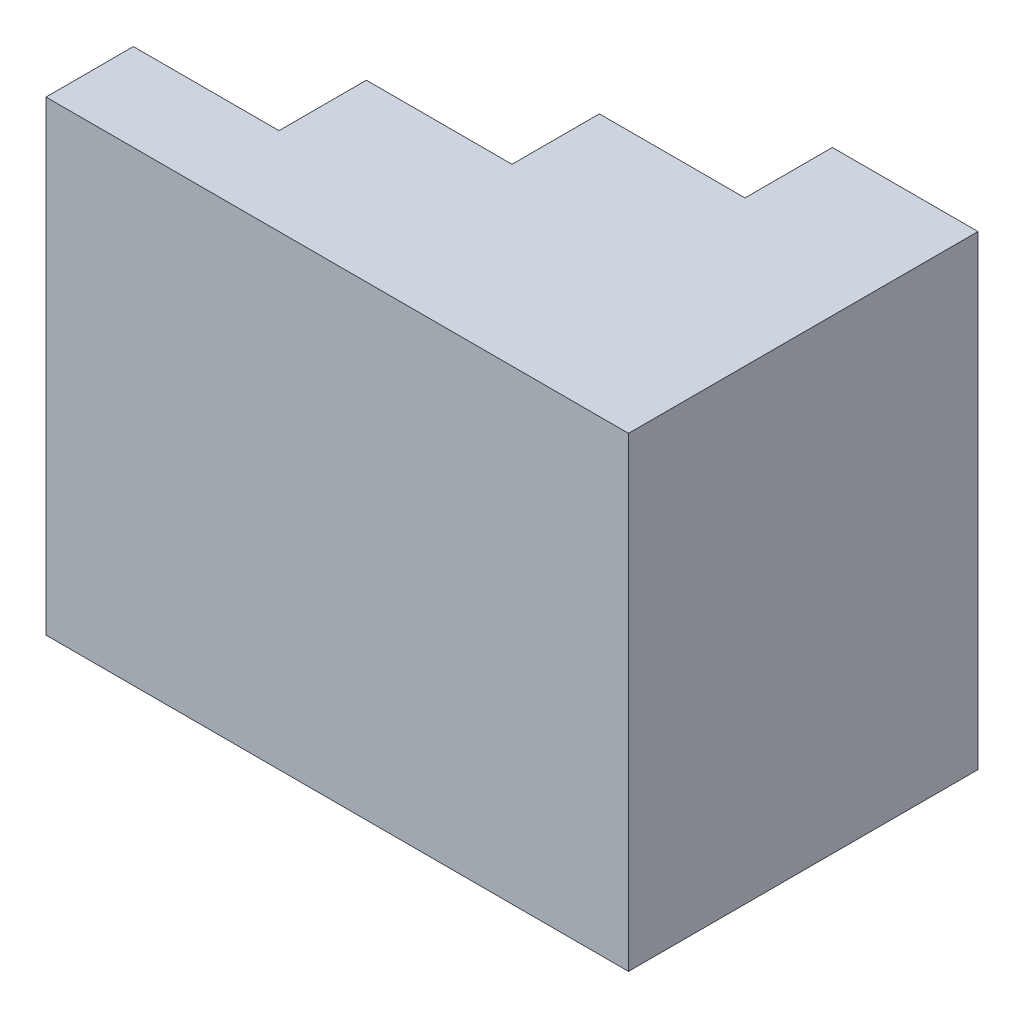
SolidWorks part; units mm, degrees
ref_plane "Front Plane" through (0, 0, 0) normal (0, 0, 1) x (1, 0, 0)
ref_plane "Top Plane" through (0, 0, 0) normal (0, 1, 0) x (1, 0, 0)
ref_plane "Right Plane" through (0, 0, 0) normal (1, 0, 0) x (0, 0, -1)
sketch "Sketch1" plane through (0, 0, 0) normal (0, 1, 0) x (1, 0, 0)
  line L0 (-50, -15) -> (-25, -15)
  line L1 (-50, -30) -> (50, -30)
  line L2 (-50, -30) -> (-50, 30)
  line L3 (-50, 30) -> (50, 30)
  line L4 (50, -30) -> (50, 30)
  line L5 (-50, -30) -> (50, 30) construction
  line L6 (-50, 30) -> (50, -30) construction
  line L7 (-25, -15) -> (-25, 0)
  line L8 (-25, 0) -> (0, 0)
  line L9 (0, 0) -> (0, 15)
  line L10 (0, 15) -> (25, 15)
  line L11 (25, 15) -> (25, 30)
  point P0 (0, 0)
  dimension "D1" = 100
  dimension "D2" = 60
  dimension "D3" = 25
extrude "Boss-Extrude1" add sketch "Sketch1" along normal blind 60 contours L11 L10 L9 L8 L7 L0 L2 L1 L4 L3 region at (12.5, 0, 7.5)
extrude "Boss-Extrude2" add sketch "Sketch1<3>" against normal blind 20 contours L10 L11 L3 L2 L0 L7 L8 L9 | L11 L10 L9 L8 L7 L0 L2 L1 L4 L3 region at (-20.8333, 0, -12.5) region at (12.5, 0, 7.5)
sketch "Sketch1<3>" plane through (0, 0, 0) normal (0, 1, 0) x (1, 0, 0) same geometry as "Sketch1"
